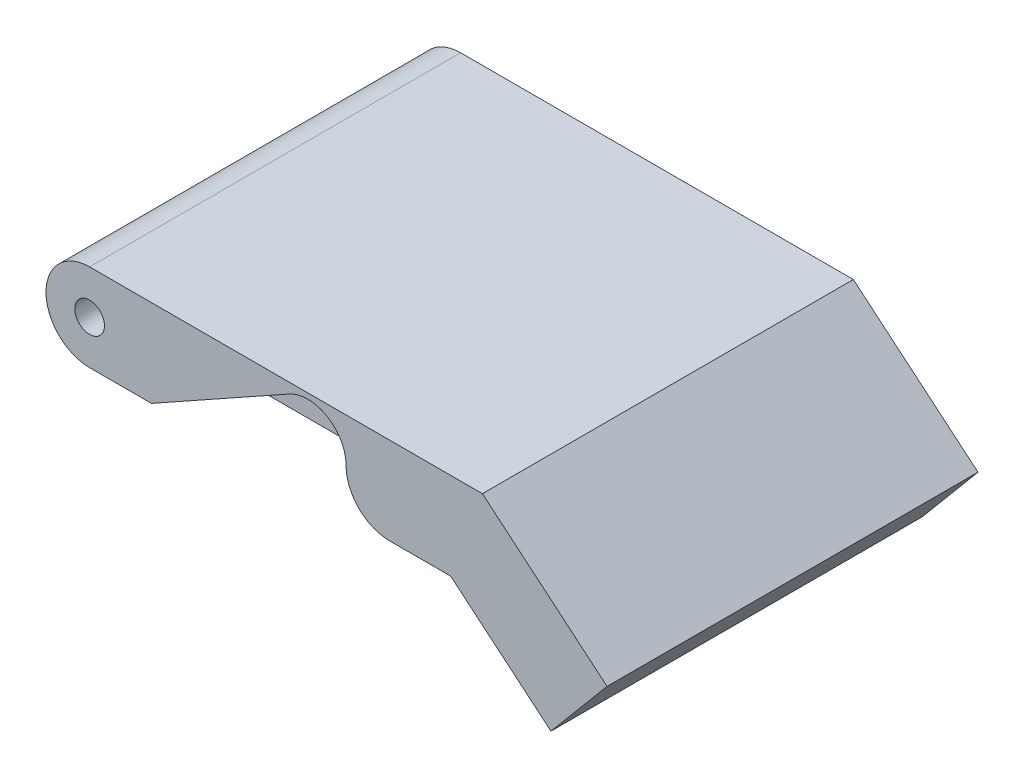
SolidWorks part; units mm, degrees
ref_plane "Front Plane" through (0, 0, 0) normal (0, 0, 1) x (1, 0, 0)
ref_plane "Top Plane" through (0, 0, 0) normal (0, 1, 0) x (1, 0, 0)
ref_plane "Right Plane" through (0, 0, 0) normal (1, 0, 0) x (0, 0, -1)
sketch "Sketch1" plane through (0, 0, 0) normal (0, 0, 1) x (1, 0, 0)
  line L0 (0, 6.35) -> (57.15, 6.35)
  line L1 (57.15, 6.35) -> (75.2841, -8.8663)
  line L2 (75.2841, -8.8663) -> (67.1207, -18.5951)
  line L3 (67.1207, -18.5951) -> (52.5276, -6.35)
  line L4 (52.5276, -6.35) -> (0, -6.35)
  arc A0 (0, 6.35) -> (0, -6.35) centre (0, 0) ccw
  dimension "D2" = 12.7
  dimension "D4" = 19.05
  dimension "D5" = 220
  dimension "D6" = 57.15
  dimension "D7" = 12.7
extrude "Boss-Extrude1" add sketch "Sketch1" along normal mid plane 53.975
sketch "Sketch2" plane through (0, 0, 26.9875) normal (0, 0, 1) x (1, 0, 0)
  line L1 (57.15, 6.35) -> (0, 6.35) construction
  circle A0 centre (0, 0) radius 2.159
  circle A1 centre (31.75, 0) radius 1.905
  dimension "D4" = 4.318
  dimension "D5" = 3.81
  dimension "D1" = 31.75
  dimension "D3" = 6.35
extrude "Cut-Extrude1" cut sketch "Sketch2" against normal through all
sketch "Sketch3" plane through (0, 0, 26.9875) normal (0, 0, 1) x (1, 0, 0)
  line L12 (0, -6.35) -> (52.5276, -6.35) construction
  line L13 (43.6563, -6.35) -> (8.9967, -6.35)
  line L17 (29.0396, 4.8503) -> (8.9967, -6.35)
  arc A11 (37.3063, 0) -> (43.6563, -6.35) centre (43.6563, 0) ccw
  arc A13 (37.3063, 0) -> (29.0396, 4.8503) centre (31.75, 0) ccw
  point P3 (31.75, 0)
  dimension "D1" = 5.5563
  dimension "D2" = 22.7533
extrude "Cut-Extrude2" cut sketch "Sketch3" against normal blind 9.525
mirror "Mirror1" about plane through (0, 0, 0) normal (0, 0, 1) of "Cut-Extrude2"
